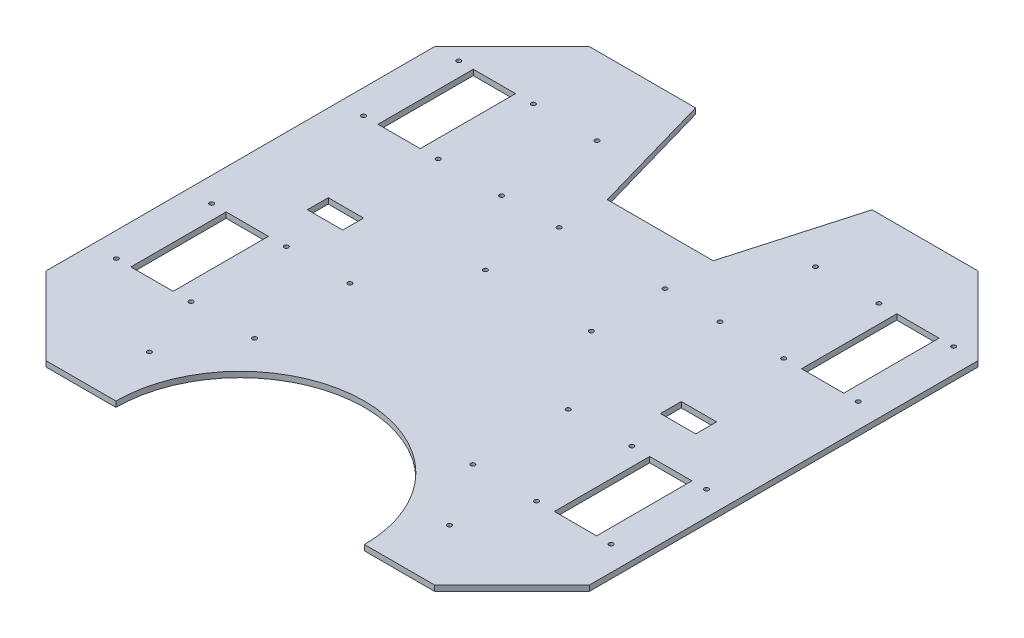
SolidWorks part; units mm, degrees
ref_plane "前视基准面" through (0, 0, 0) normal (0, 0, 1) x (1, 0, 0)
ref_plane "上视基准面" through (0, 0, 0) normal (0, 1, 0) x (1, 0, 0)
ref_plane "右视基准面" through (0, 0, 0) normal (1, 0, 0) x (0, 0, -1)
other "Configuration Table"
sketch "草图1" plane through (0, 0, 0) normal (0, 1, 0) x (1, 0, 0)
  line B0 (-154.363, -59.6711) -> (-154.363, 8.9089)
  line B1 (-154.363, 8.9089) -> (-184.763, 8.9089)
  line B2 (-184.763, 8.9089) -> (-184.763, -59.6711)
  line B3 (-184.763, -59.6711) -> (-154.363, -59.6711)
  line B4 (150.357, 118.1289) -> (150.357, 186.7089)
  line B5 (150.357, 186.7089) -> (119.957, 186.7089)
  line B6 (119.957, 186.7089) -> (119.957, 118.1289)
  line B7 (119.957, 118.1289) -> (150.357, 118.1289)
  line B8 (119.957, 8.9089) -> (119.957, -59.6711)
  line B9 (119.957, -59.6711) -> (150.357, -59.6711)
  line B10 (150.357, -59.6711) -> (150.357, 8.9089)
  line B11 (150.357, 8.9089) -> (119.957, 8.9089)
  line B12 (-154.363, 118.1289) -> (-154.363, 186.7089)
  line B13 (-154.363, 186.7089) -> (-184.763, 186.7089)
  line B14 (-184.763, 186.7089) -> (-184.763, 118.1289)
  line B15 (-184.763, 118.1289) -> (-154.363, 118.1289)
  line B16 (-131.503, 39.5089) -> (-131.503, 54.5089)
  line B17 (-131.503, 54.5089) -> (-156.903, 54.5089)
  line B18 (-156.903, 54.5089) -> (-156.903, 39.5089)
  line B19 (-156.903, 39.5089) -> (-131.503, 39.5089)
  line B20 (122.497, 39.5089) -> (122.497, 54.5089)
  line B21 (122.497, 54.5089) -> (97.097, 54.5089)
  line B22 (97.097, 54.5089) -> (97.097, 39.5089)
  line B23 (97.097, 39.5089) -> (122.497, 39.5089)
  line B24 (-212.783, -92.6911) -> (-212.783, 186.7089)
  line B25 (-156.903, 242.5889) -> (-212.783, 186.7089)
  line B26 (-80.703, 242.5889) -> (-156.903, 242.5889)
  line B27 (-80.703, 242.5889) -> (-55.303, 153.6889)
  line B28 (-55.303, 153.6889) -> (20.897, 153.6889)
  line B29 (46.297, 242.5889) -> (20.897, 153.6889)
  line B30 (122.497, 242.5889) -> (46.297, 242.5889)
  line B31 (122.497, 242.5889) -> (178.377, 186.7089)
  line B32 (178.377, -92.6911) -> (178.377, 186.7089)
  line B33 (178.377, -92.6911) -> (122.497, -148.5711)
  line B34 (122.497, -148.5711) -> (72.205, -148.5711)
  line B35 (-106.611, -148.5711) -> (-156.903, -148.5711)
  line B36 (-156.903, -148.5711) -> (-212.783, -92.6911)
  circle B37 centre (-141.489, 186.7089) radius 1.55
  circle B38 centre (20.897, 66.0089) radius 1.55
  circle B39 centre (90.747, -105.9911) radius 1.55
  circle B40 centre (-125.153, -105.9911) radius 1.55
  circle B41 centre (-141.489, 118.1289) radius 1.55
  circle B42 centre (-95.769, 118.1289) radius 1.55
  circle B43 centre (107.083, 118.1289) radius 1.55
  circle B44 centre (-141.489, 8.9089) radius 1.55
  circle B45 centre (61.363, 118.1289) radius 1.55
  circle B46 centre (61.363, 186.7089) radius 1.55
  circle B47 centre (-141.489, -59.6711) radius 1.55
  circle B48 centre (-95.769, -59.6711) radius 1.55
  circle B49 centre (-95.769, 186.7089) radius 1.55
  circle B50 centre (107.083, -59.6711) radius 1.55
  circle B51 centre (61.363, -59.6711) radius 1.55
  circle B52 centre (107.083, 186.7089) radius 1.55
  circle B53 centre (160.797, 186.7089) radius 1.55
  circle B54 centre (-195.203, 118.1289) radius 1.55
  circle B55 centre (-195.203, 186.7089) radius 1.55
  circle B56 centre (160.797, 8.9089) radius 1.55
  circle B57 centre (-55.303, 66.0089) radius 1.55
  circle B58 centre (20.897, 119.0089) radius 1.55
  circle B59 centre (-55.303, 119.0089) radius 1.55
  circle B60 centre (160.797, 118.1289) radius 1.55
  circle B61 centre (107.083, 8.9089) radius 1.55
  circle B62 centre (61.363, 8.9089) radius 1.55
  circle B63 centre (-95.769, 8.9089) radius 1.55
  circle B64 centre (-195.203, 8.9089) radius 1.55
  circle B65 centre (-195.203, -59.6711) radius 1.55
  circle B66 centre (160.797, -59.6711) radius 1.55
  arc B67 (72.205, -148.5711) -> (-106.611, -148.5711) centre (-17.203, -148.5711) ccw
sketch_block_instance "chassis-1"
sketch_block "chassis"
extrude "凸台-拉伸1" add sketch "草图1" along normal blind 4
